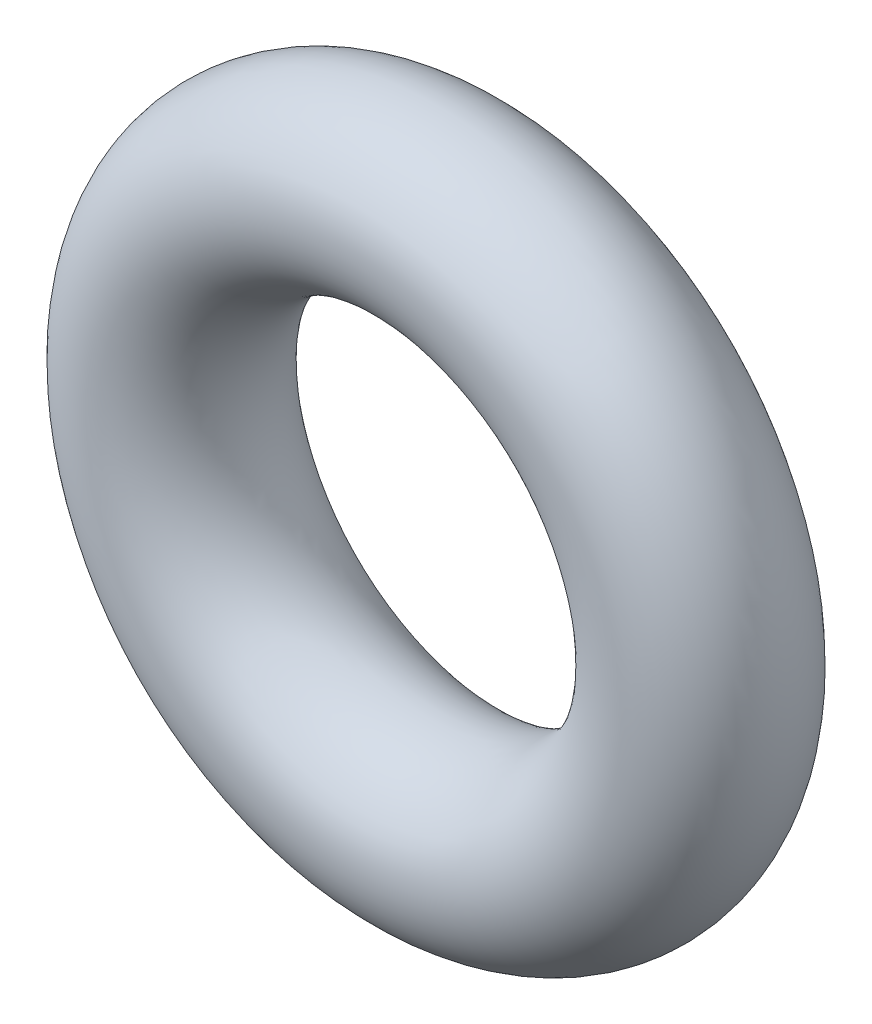
SolidWorks part; units mm, degrees
ref_plane "Top" through (0, 0, 0) normal (0, 0, 1) x (1, 0, 0)
ref_plane "Front" through (0, 0, 0) normal (0, 1, 0) x (1, 0, 0)
ref_plane "Right" through (0, 0, 0) normal (1, 0, 0) x (0, 0, -1)
sketch "O-Ring Sketch" plane through (0, 0, 0) normal (0, 1, 0) x (1, 0, 0)
  line L0 (0, 0) -> (0, 0.5) construction
  line L1 (1, -0.5) -> (2, -0.5) construction
  line L2 (1, -0.5) -> (1, 0.5) construction
  line L3 (1, 0.5) -> (2, 0.5) construction
  line L4 (2, -0.5) -> (2, 0.5) construction
  line L5 (1.5, 0.5) -> (1.5, -0.5) construction
  line L6 (1, 0) -> (2, 0) construction
  line L7 (-1, -0.5) -> (-1, 0.5) construction
  line L8 (-2, -0.5) -> (-2, 0.5) construction
  circle A0 centre (1.5, 0) radius 0.5
  point P275 (1.5, 0)
  dimension "Inner Diameter" = 2
  dimension "Outer Diameter" = 4
revolve "O-Ring Revolve" add sketch "O-Ring Sketch" angle 360 about L0
ref_axis "Centerline Axis" through (0, 0, -80.9) along (0, 0, 1)
equation "\"M2 Close Fit Hole\"= 2.2"
equation "\"M2.5 Close Fit Hole\"= 2.7"
equation "\"M3 Close Fit Hole\"= 3.2"
equation "\"M4 Close Fit Hole\"= 4.3"
equation "\"M5 Close Fit Hole\"= 5.3"
equation "\"M6 Close Fit Hole\"= 6.3"
equation "\"M7 Close Fit Hole\"= 7.4"
equation "\"M8 Close Fit Hole\"= 8.4"
equation "\"M2 Tap Hole 75%\"= 1.6"
equation "\"M3 Tap Hole 75%\"= 2.5"
equation "\"M4 Tap Hole 75%\"= 3.3"
equation "\"M5 Tap Hole 75%\"= 4.2"
equation "\"M6 Tap Hole 75%\"= 5"
equation "\"M7 Tap Hole 75%\"= 6"
equation "\"M8 Tap Hole 75%\"= 6.8"
